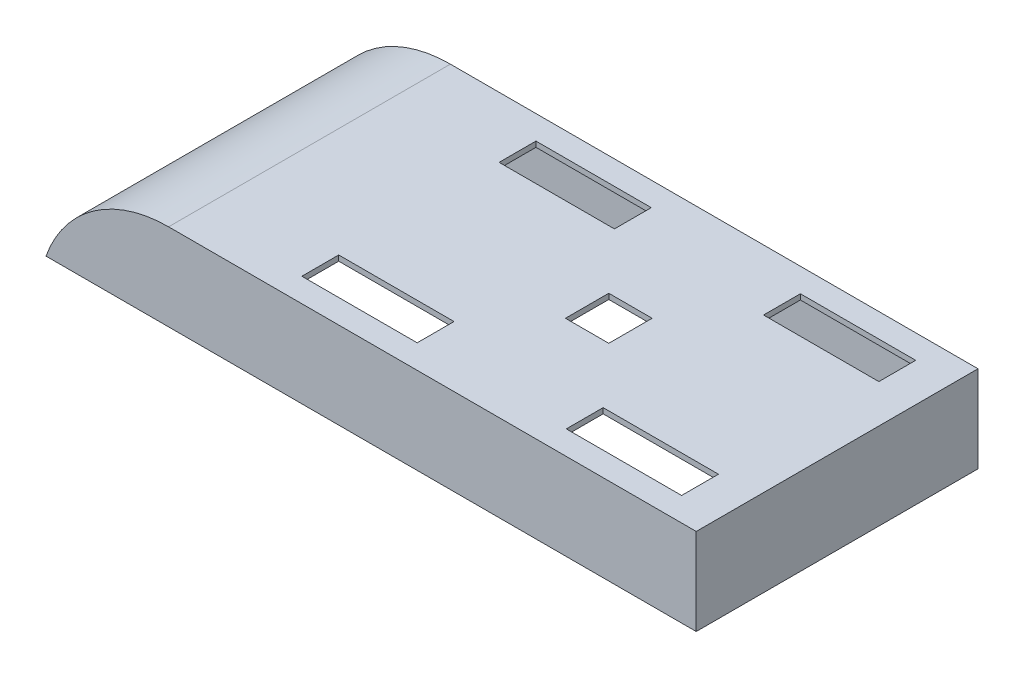
SolidWorks part; units mm, degrees
ref_plane "Front Plane" through (0, 0, 0) normal (0, 0, 1) x (1, 0, 0)
ref_plane "Top Plane" through (0, 0, 0) normal (0, 1, 0) x (1, 0, 0)
ref_plane "Right Plane" through (0, 0, 0) normal (1, 0, 0) x (0, 0, -1)
sketch "Sketch1" plane through (0, 0, 0) normal (0, 1, 0) x (1, 0, 0)
  line L1 (0, 0) -> (762, 0)
  line L2 (0, 0) -> (0, 330.2)
  line L3 (0, 330.2) -> (762, 330.2)
  line L4 (762, 0) -> (762, 330.2)
  dimension "D1" = 762
  dimension "D2" = 330.2
extrude "Boss-Extrude1" add sketch "Sketch1" along normal blind 101.6
fillet "Fillet1" radius 152.4 1 edges at (0, 101.6, -165.1)
shell "Shell1" thickness 6.35 removed face at (381, 0, -165.1)
sketch "Sketch3" plane through (0, 101.6, 0) normal (0, 1, 0) x (1, 0, 0)
  line L0 (271.9211, 27.935) -> (407.0491, 27.935)
  line L17 (407.0491, 27.935) -> (407.0491, 71.115)
  line L18 (143.6841, 165.1) -> (762, 165.1) construction
  line L19 (143.6841, 330.2) -> (143.6841, 0) construction
  line L20 (762, 0) -> (762, 330.2) construction
  line L21 (494.4251, 330.2) -> (494.4251, 0) construction
  line L23 (716.9291, 259.085) -> (581.8011, 259.085)
  line L24 (581.8011, 302.265) -> (581.8011, 259.085)
  line L25 (716.9291, 302.265) -> (581.8011, 302.265)
  line L26 (716.9291, 302.265) -> (716.9291, 259.085)
  line L27 (716.9291, 27.935) -> (716.9291, 71.115)
  line L28 (716.9291, 27.935) -> (581.8011, 27.935)
  line L29 (581.8011, 27.935) -> (581.8011, 71.115)
  line L30 (716.9291, 71.115) -> (581.8011, 71.115)
  line L42 (271.9211, 71.115) -> (407.0491, 71.115)
  line L43 (271.9211, 27.935) -> (271.9211, 71.115)
  line L44 (271.9211, 302.265) -> (271.9211, 259.085)
  line L45 (271.9211, 302.265) -> (407.0491, 302.265)
  line L46 (407.0491, 302.265) -> (407.0491, 259.085)
  line L47 (271.9211, 259.085) -> (407.0491, 259.085)
  line L52 (762, 330.2) -> (143.6841, 330.2) construction
  line L66 (469.0251, 139.7) -> (519.8251, 139.7)
  line L67 (469.0251, 139.7) -> (469.0251, 190.5)
  line L68 (469.0251, 190.5) -> (519.8251, 190.5)
  line L69 (519.8251, 139.7) -> (519.8251, 190.5)
  line L70 (494.4251, 190.5) -> (494.4251, 139.7) construction
  line L71 (469.0251, 165.1) -> (519.8251, 165.1) construction
  point P10 (649.3651, 259.085)
  point P11 (494.4251, 165.1)
  dimension "D1" = 45.0709
  dimension "D2" = 154.94
  dimension "D3" = 43.18
  dimension "D4" = 135.128
  dimension "D5" = 50.8
  dimension "D6" = 50.8
  dimension "D7" = 274.33
extrude "Cut-Extrude1" cut sketch "Sketch3" against normal blind 127.762
